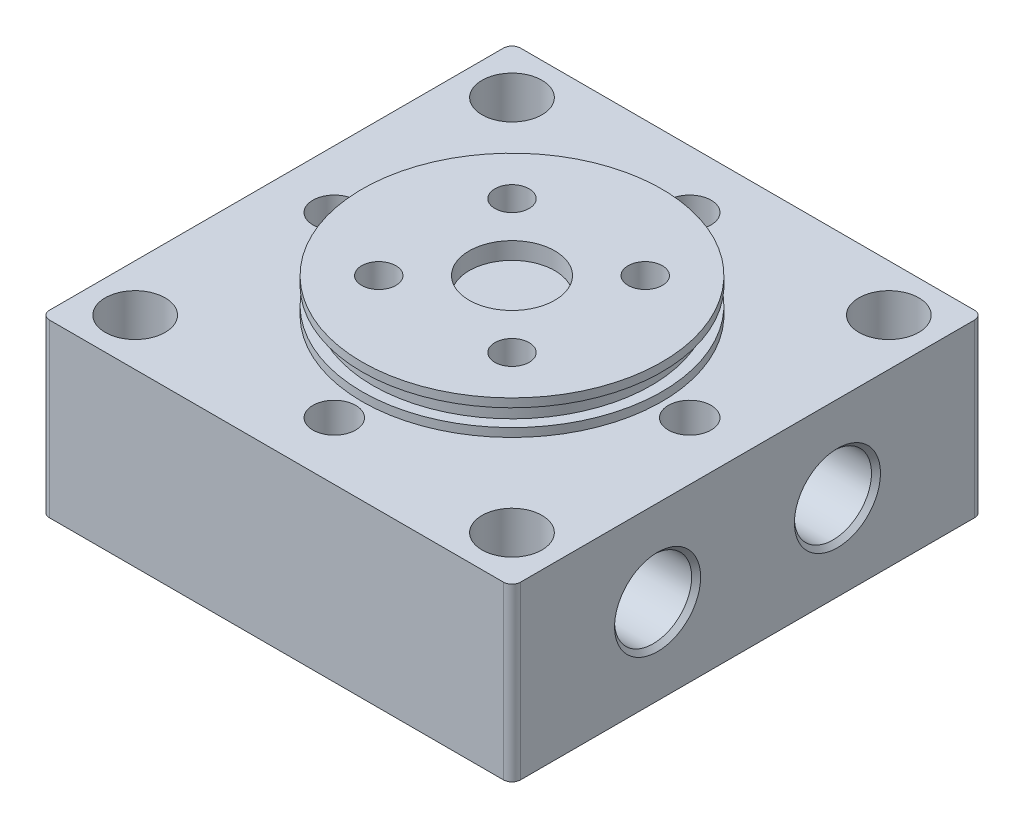
SolidWorks part; units mm, degrees
ref_plane "前视基准面" through (0, 0, 0) normal (0, 0, 1) x (1, 0, 0)
ref_plane "上视基准面" through (0, 0, 0) normal (0, 1, 0) x (1, 0, 0)
ref_plane "右视基准面" through (0, 0, 0) normal (1, 0, 0) x (0, 0, -1)
other "Configuration Table"
sketch "草图1" plane through (0, 0, 0) normal (0, 1, 0) x (1, 0, 0)
  line L1 (-27.5, 27.5) -> (27.5, 27.5)
  line L2 (-27.5, 27.5) -> (-27.5, -27.5)
  line L3 (-27.5, -27.5) -> (27.5, -27.5)
  line L4 (27.5, 27.5) -> (27.5, -27.5)
  line L5 (-27.5, 27.5) -> (27.5, -27.5) construction
  line L6 (-27.5, -27.5) -> (27.5, 27.5) construction
  point P0 (0, 0)
  dimension "D1" = 55
  dimension "D2" = 55
extrude "凸台-拉伸1" add sketch "草图1" along normal mid plane 20
sketch "草图2" plane through (0, 10, 0) normal (0, 1, 0) x (1, 0, 0)
  circle A0 centre (0, 0) radius 17.5
  dimension "D1" = 35
extrude "凸台-拉伸2" add sketch "草图2" along normal blind 1
sketch "草图3" plane through (0, 11, 0) normal (0, 1, 0) x (1, 0, 0)
  circle A0 centre (0, 0) radius 16.25
  dimension "D1" = 32.5
extrude "凸台-拉伸3" add sketch "草图3" along normal blind 2
sketch "草图4" plane through (0, 13, 0) normal (0, 1, 0) x (1, 0, 0)
  circle A0 centre (0, 0) radius 17.5
  dimension "D1" = 35
extrude "凸台-拉伸4" add sketch "草图4" along normal blind 1
sketch "草图5" plane through (0, -10, 0) normal (0, -1, 0) x (1, 0, 0)
  circle A1 centre (0, 0) radius 20.75 construction
  circle A2 centre (0, 20.75) radius 4.25
  dimension "D1" = 41.5
  dimension "D2" = 8.5
extrude "切除-拉伸1" cut sketch "草图5" against normal blind 3
sketch "草图6" plane through (0, -7, 0) normal (0, -1, 0) x (1, 0, 0)
  circle A0 centre (0, 20.75) radius 2.5
  dimension "D1" = 5
extrude "切除-拉伸2" cut sketch "草图6" against normal through all
ref_axis "基准轴1" through (0, 14, 0) along (0, -1, 0)
sketch "草图7" plane through (0, -10, 0) normal (0, -1, 0) x (1, 0, 0)
  circle A0 centre (-22, 22) radius 3.5
  dimension "D1" = 7
  dimension "D2" = 22
  dimension "D3" = 22
extrude "切除-拉伸3" cut sketch "草图7" against normal through all
pattern_circular "阵列(圆周)1" count 4 over 360 about axis through (0, 14, 0) along (0, -1, 0) of "切除-拉伸1", "切除-拉伸2", "切除-拉伸3"
hole_wizard "M10x1.0 螺纹孔1" positions "草图8" profile "草图9" tap size "M10x1.0" standard "GB"
sketch "草图8" plane through (-27.5, 0, 0) normal (-1, 0, 0) x (0, 0, 1)
  line L0 (-27.5, -10) -> (27.5, -10) construction
  line L1 (-27.5, 10) -> (-27.5, -10) construction
  point P0 (-10.5, 0)
  dimension "D1" = 10
  dimension "D2" = 17
sketch "草图9" plane through (-27.5, 0, -10.5) normal (0, 1, 0) x (0, 0, 1)
  line L0 (0, 0) -> (0, 24.7039)
  line L1 (0, 24.7039) -> (4.5, 22)
  line L2 (4.5, 22) -> (4.5, 0.525)
  line L3 (4.5, 0.525) -> (5.025, 0)
  line L5 (5.025, 0) -> (0, 0)
  line L6 (-4.5, 0.525) -> (-5.025, 0) construction
  line L10 (0, 24.7039) -> (-4.5, 22) construction
  line L11 (0, -6.35) -> (0, 107.95) construction
  dimension "螺纹孔钻头直径" = 9
  dimension "螺纹孔钻头深度" = 22
  dimension "近端锥形沉头孔直径" = 10.05
  dimension "近端锥形沉头孔角度" = 90
  dimension "导头角度" = 118
cosmetic thread "孔螺蚊线1" parameters "D1"=10, "D2"=10
mirror "镜向1" about plane through (0, 0, 0) normal (1, 0, 0) of "M10x1.0 螺纹孔1" second plane through (0, 0, 0) second plane normal (0, 0, 1)
sketch "草图10" plane through (0, 14, 0) normal (0, 1, 0) x (1, 0, 0)
  circle A0 centre (0, 0) radius 5
  dimension "D1" = 10
extrude "切除-拉伸4" cut sketch "草图10" against normal blind 2
sketch "草图11" plane through (0, 14, 0) normal (0, 1, 0) x (1, 0, 0)
  line L0 (-17.5, 0) -> (17.5, 0) construction
  line L1 (0, 0) -> (12.3744, 12.3744) construction
  circle A0 centre (0, 0) radius 11 construction
  circle A1 centre (0, 0) radius 17.5 construction
  circle A2 centre (0, 0) radius 17.5 construction
  circle A3 centre (7.7782, 7.7782) radius 2
  dimension "D1" = 22
  dimension "D3" = 4
  dimension "D2" = 45
extrude "切除-拉伸5" cut sketch "草图11" against normal blind 14
pattern_circular "阵列(圆周)2" count 4 over 360 about axis through (0, 14, 0) along (0, 1, 0) of "切除-拉伸5"
fillet "圆角1" radius 1 4 edges at (-27.5, 0, -27.5) (27.5, 0, -27.5) (27.5, 0, 27.5) (-27.5, 0, 27.5)
chamfer "倒角1" distance 0.5 angle 45 4 edges at (-16.5, -10, 0) (0, -10, -16.5) (0, -10, 16.5) (16.5, -10, 0)
chamfer "倒角2" distance 1 angle 45 4 edges at (-22, -10, 18.5) (-18.5, -10, -22) (22, -10, -18.5) (18.5, -10, 22)
